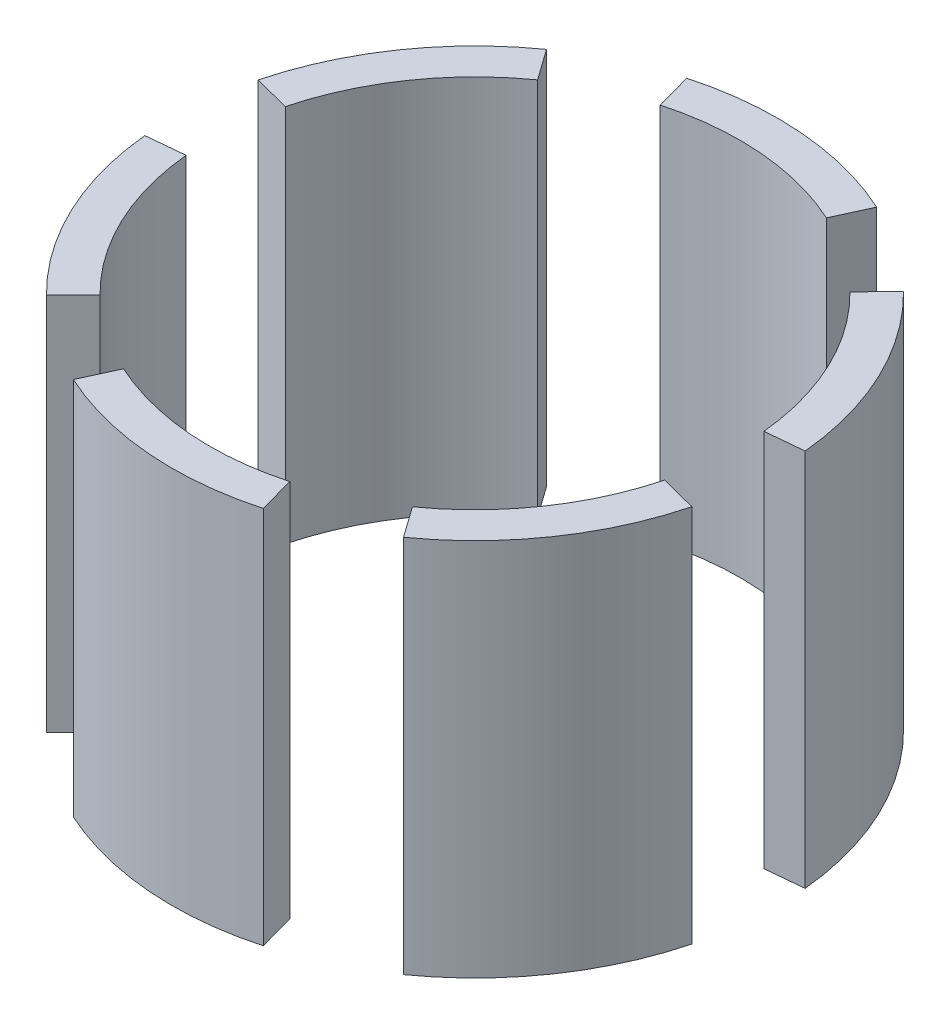
SolidWorks part; units mm, degrees
ref_plane "Front Plane" through (0, 0, 0) normal (0, 0, 1) x (1, 0, 0)
ref_plane "Top Plane" through (0, 0, 0) normal (0, 1, 0) x (1, 0, 0)
ref_plane "Right Plane" through (0, 0, 0) normal (1, 0, 0) x (0, 0, -1)
sketch "Sketch6" plane through (0, 0, 0) normal (0, 1, 0) x (1, 0, 0)
  line L0 (-8.327, -18.1841) -> (0, 0)
  line L1 (0, 0) -> (5.3096, -19.2823)
  line L2 (-19.9114, -1.8806) -> (0, 0)
  line L3 (0, 0) -> (-14.0442, -14.2394)
  line L4 (-11.5844, 16.3035) -> (0, 0)
  line L5 (0, 0) -> (-19.3538, 5.0429)
  line L6 (8.327, 18.1841) -> (0, 0)
  line L7 (0, 0) -> (-5.3096, 19.2823)
  line L8 (19.9114, 1.8806) -> (0, 0)
  line L9 (0, 0) -> (14.0442, 14.2394)
  line L10 (11.5844, -16.3035) -> (0, 0)
  line L11 (0, 0) -> (19.3538, -5.0429)
  arc A0 (5.3096, -19.2823) -> (-8.327, -18.1841) centre (0, 0) cw
  arc A1 (-14.0442, -14.2394) -> (-19.9114, -1.8806) centre (0, 0) cw
  arc A2 (-19.3538, 5.0429) -> (-11.5844, 16.3035) centre (0, 0) cw
  arc A3 (-5.3096, 19.2823) -> (8.327, 18.1841) centre (0, 0) cw
  arc A4 (14.0442, 14.2394) -> (19.9114, 1.8806) centre (0, 0) cw
  arc A5 (19.3538, -5.0429) -> (11.5844, -16.3035) centre (0, 0) cw
  point P17 (0, 0)
  dimension "D1" = 6
extrude "Boss-Extrude2" add sketch "Sketch6" along normal blind 25 contours A2 L5 L4 | A1 L3 L2 | A0 L1 L0 | A5 L11 L10 | A4 L9 L8 | A3 L7 L6 region at (-11.8018, 0, 5.6028) region at (-10.753, 0, -7.4193) region at (1.0487, 0, -13.022) region at (11.8018, 0, -5.6028) region at (10.753, 0, 7.4193) region at (-1.0487, 0, 13.022)
sketch "Sketch7" plane through (0, 0, 0) normal (0, 1, 0) x (1, 0, 0)
  circle A0 centre (0, 0) radius 17.5
extrude "Cut-Extrude1" cut sketch "Sketch7" along normal blind 25
